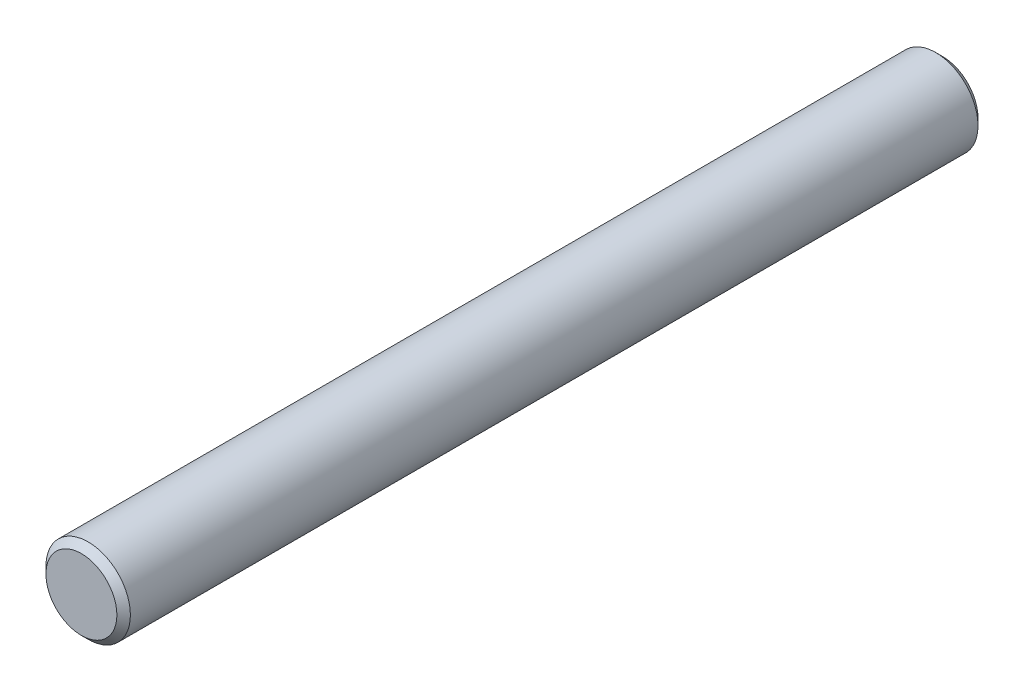
SolidWorks part; units mm, degrees
material "AISI 1020"
ref_plane "Front" through (0, 0, 0) normal (0, 0, 1) x (1, 0, 0)
ref_plane "Top" through (0, 0, 0) normal (0, 1, 0) x (1, 0, 0)
ref_plane "Right" through (0, 0, 0) normal (1, 0, 0) x (0, 0, -1)
ref_axis "side-side" through (80.9, 0, 0) along (-1, 0, 0)
ref_axis "up-down" through (0, 50, 0) along (0, -1, 0)
ref_axis "front-back" through (0, 0, -80.9) along (0, 0, 1)
sketch "Sketch1" plane through (0, 0, 0) normal (0, 0, 1) x (1, 0, 0)
  circle A0 centre (0, 0) radius 2.3813
  dimension "D1" = 4.7625
extrude "Boss-Extrude1" add sketch "Sketch1" along normal blind 48.56
chamfer "Chamfer1" distance 0.381 angle 45 2 edges at (2.3813, 0, 0) (2.3813, 0, 48.56)
